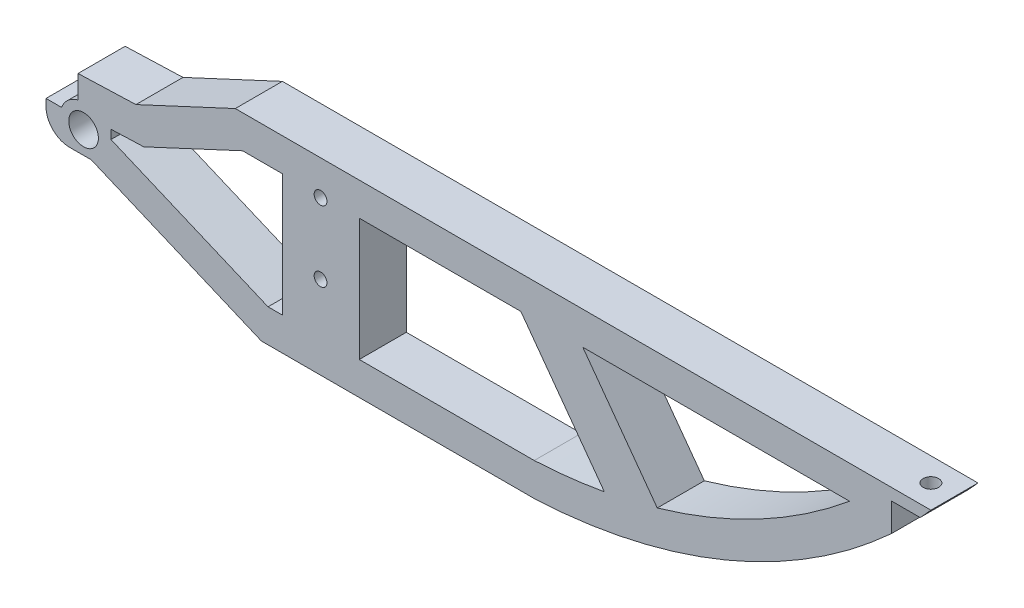
SolidWorks part; units mm, degrees
ref_plane "Front Plane" through (0, 0, 0) normal (0, 0, 1) x (1, 0, 0)
ref_plane "Top Plane" through (0, 0, 0) normal (0, 1, 0) x (1, 0, 0)
ref_plane "Right Plane" through (0, 0, 0) normal (1, 0, 0) x (0, 0, -1)
sketch "Sketch1" plane through (0, 0, 0) normal (0, 0, 1) x (1, 0, 0)
  line L1 (120.65, 25.4) -> (-120.65, 25.4)
  line L2 (120.65, 25.4) -> (120.65, -25.4)
  line L3 (120.65, -25.4) -> (-120.65, -25.4)
  line L4 (-120.65, 25.4) -> (-120.65, -25.4)
  line L5 (120.65, 25.4) -> (-120.65, -25.4) construction
  line L6 (120.65, -25.4) -> (-120.65, 25.4) construction
  point P0 (0, 0)
  dimension "D1" = 241.3
  dimension "D2" = 50.8
extrude "Boss-Extrude1" add sketch "Sketch1" along normal blind 12.7
sketch "Sketch3" plane through (0, 0, 12.7) normal (0, 0, 1) x (1, 0, 0)
  line L0 (0, 0) -> (-120.65, 0) construction
  line L1 (-120.65, 25.4) -> (-120.65, -25.4) construction
  circle A0 centre (-107.95, 0) radius 4
  dimension "D2" = 8
  dimension "D1" = 12.7
extrude "Cut-Extrude1" cut sketch "Sketch3" against normal through all
sketch "Sketch5" plane through (0, 0, 12.7) normal (0, 0, 1) x (1, 0, 0)
  line L0 (-120.65, -25.4) -> (120.65, -25.4) construction
  line L1 (-105.8942, -6.008) -> (-59.9903, -25.4)
  line L2 (-107.95, 6.35) -> (-67.0151, 25.4)
  line L3 (120.65, 25.4) -> (-120.65, 25.4) construction
  line L4 (-67.0151, 25.4) -> (-120.65, 25.4)
  line L5 (-120.65, 25.4) -> (-120.65, -25.4)
  line L6 (-120.65, -25.4) -> (-59.9903, -25.4)
  line L7 (120.65, 25.4) -> (120.65, -25.4)
  line L8 (120.65, -25.4) -> (0, -25.4)
  line L9 (-109.9582, -6.0241) -> (-105.8942, -6.008)
  line L10 (-118.0862, -6.0241) -> (-109.9582, -6.0241)
  line L11 (-118.0862, -6.0241) -> (-118.0862, 2.2309)
  line L12 (-118.0862, 2.2309) -> (-113.8952, 2.2309)
  arc A0 (0, -25.4) -> (120.65, 25.4) centre (6.9175, 126.8429) ccw
  arc A1 (-109.9582, -6.0241) -> (-105.8942, -6.008) centre (-107.95, 0) ccw construction
  arc A2 (-107.95, 6.35) -> (-113.8952, 2.2309) centre (-107.95, 0) ccw
  point P15 (-116.1445, -2.9908)
  line M3 (-120.65, 25.4) -> (-120.65, -25.4)
  line M4 (-120.65, -25.4) -> (120.65, -25.4)
  line M5 (120.65, -25.4) -> (120.65, 25.4)
  line M6 (120.65, 25.4) -> (-120.65, 25.4)
  dimension "D1" = 152.4
  dimension "D2" = 12.7
  dimension "D3" = 45.1505
  dimension "D4" = 45.9039
  dimension "D5" = 8.255
  dimension "D6" = 4.191
  dimension "D7" = 8.128
extrude "Cut-Extrude2" cut sketch "Sketch5" against normal through all contours A2 L2 L1 M6 M3 M4 | A0 L8 M5 region at (-83.2502, -16.4329, 12.7) region at (93.5193, -10.6939, 12.7)
sketch "Sketch6" plane through (0, 0, 12.7) normal (0, 0, 1) x (1, 0, 0)
  line L0 (-107.95, 0) -> (91.396, 0) construction
  arc A0 (13.8349, -25.4) -> (120.65, 25.4) centre (6.9175, 126.8429) ccw construction
  circle A1 centre (19.05, 0) radius 3.1347
  dimension "D1" = 127
sketch "Sketch7" plane through (0, 0, 0) normal (0, 0, -1) x (-1, 0, 0)
  line L0 (44.0204, -2.9977) -> (44.0204, 16.0523) construction
  point P3 (44.0204, -2.9977)
  point P4 (44.0204, 16.0523)
  dimension "D1" = 19.05
sketch "Sketch8" plane through (0, 0, 0) normal (0, 0, -1) x (-1, 0, 0)
  point P0 (44.0204, 16.0523)
  point P3 (44.0204, -2.9977)
hole_wizard "Tap Drill for #8-32 Tap1" positions "Sketch8" profile "Sketch9" hole size "#8-32" standard "ANSI Inch" end condition through all
sketch "Sketch9" plane through (-44.0204, 16.0523, 0) normal (1, 0, 0) x (0, 1, 0)
  line L0 (0, 0) -> (0, 12.7)
  line L1 (0, 12.7) -> (1.7272, 12.7)
  line L2 (1.7272, 12.7) -> (1.7272, 0)
  line L5 (1.7272, 0) -> (0, 0)
  line L11 (0, -6.35) -> (0, 107.95) construction
  dimension "Thru Hole Dia." = 3.4544
  dimension "Thru Hole Depth" = 12.7
ref_plane "Plane1" through (-114.3, 0, 0) normal (-1, 0, 0) x (0, 0, 1)
sketch "Sketch10" plane through (-114.3, 0, 0) normal (-1, 0, 0) x (0, 0, 1)
  line L0 (0, 0) -> (12.7, 0) construction
  line L1 (12.7, -3.1347) -> (12.7, 3.1347) construction
  circle A0 centre (6.0894, 0) radius 1.905
  dimension "D1" = 3.81
extrude "Cut-Extrude3" cut sketch "Sketch10" against normal blind 5.08
sketch "Sketch11" plane through (0, 0, 12.7) normal (0, 0, 1) x (1, 0, 0)
  line L0 (-93.8249, 12.9234) -> (-109.4459, 12.9234) construction
  line L1 (-107.95, 6.35) -> (-67.0151, 25.4) construction
  line L2 (-109.4459, 12.9234) -> (-109.4459, 5.6538) construction
  line L3 (-93.8249, 12.9234) -> (-109.4459, 5.6538)
  line L4 (-93.8249, 12.9234) -> (-109.4459, 12.3779)
  line L5 (-109.4459, 12.3779) -> (-109.4459, 5.6538)
  circle A1 centre (-107.95, 0) radius 4 construction
  dimension "D1" = 15.621
  dimension "D2" = 5.6538
  dimension "D3" = 178
extrude "Boss-Extrude2" add sketch "Sketch11" against normal up to surface (12.7 mm away) up to face at (-45.7476, 16.0523, 0)
sketch "Sketch12" plane through (0, 0, 12.7) normal (0, 0, 1) x (1, 0, 0)
  line L1 (10.0217, 16.51) -> (-33.5733, 16.51)
  line L24 (-33.5733, 16.51) -> (-33.5733, -16.51)
  line L25 (-54.2244, 16.51) -> (-54.2244, -16.51)
  line L26 (-54.2244, 16.51) -> (-65.0478, 16.51)
  line L27 (-33.5733, -16.51) -> (13.63, -16.51)
  line L28 (10.0217, 16.51) -> (32.5572, -14.3581)
  line L29 (26.7339, 16.51) -> (46.8231, -11.0072)
  line L30 (-100.5559, 3.793) -> (-100.5559, 1.3876)
  line L31 (-100.5559, 1.3876) -> (-58.1896, -16.51)
  line L32 (-58.1896, -16.51) -> (13.63, -16.51)
  line L33 (98.6876, 16.51) -> (-65.0478, 16.51)
  line L34 (-65.0478, 16.51) -> (-91.7106, 4.1018)
  line L35 (-91.7106, 4.1018) -> (-100.5559, 3.793)
  line L36 (-100.5559, 3.793) -> (-100.5559, 1.3876)
  line L37 (-100.5559, 1.3876) -> (-58.1896, -16.51)
  line L38 (-58.1896, -16.51) -> (-54.2244, -16.51)
  line L39 (98.6876, 16.51) -> (26.7339, 16.51)
  line L40 (-65.0478, 16.51) -> (-91.7106, 4.1018)
  line L41 (-91.7106, 4.1018) -> (-100.5559, 3.793)
  arc A0 (46.8231, -11.0072) -> (98.6876, 16.51) centre (6.9175, 126.8429) ccw
  arc A10 (13.63, -16.51) -> (98.6876, 16.51) centre (6.9175, 126.8429) ccw
  arc A11 (13.63, -16.51) -> (32.5572, -14.3581) centre (6.9175, 126.8429) ccw
  dimension "D1" = 8.89
extrude "Cut-Extrude4" cut sketch "Sketch12" against normal through all
sketch "Sketch13" plane through (0, 0, 12.7) normal (0, 0, 1) x (1, 0, 0)
  line L0 (-79.3724, -17.2121) -> (-87.4623, -19.4143)
  line L1 (-105.8942, -6.008) -> (-59.9903, -25.4) construction
  line L2 (-87.4623, -19.4143) -> (-89.1909, -13.0643)
  line L4 (-79.3724, -17.2121) -> (-89.1909, -13.0643)
  circle A0 centre (-107.95, 0) radius 4 construction
  dimension "D1" = 90
  dimension "D2" = 6.35
  dimension "D3" = 22.86
fillet "Fillet1" radius 6.35 1 edges at (-118.0862, -6.0241, 6.35)
sketch "Sketch14" plane through (0.0221, -5.5891, 0) normal (0.004, -1, 0) x (1, 0.004, 0)
  line L0 (-109.9812, 0) -> (-109.9812, 12.7) construction
  line L2 (-109.9812, 6.35) -> (-105.9171, 6.35) construction
  line L3 (-105.9171, 0) -> (-105.9171, 12.7) construction
  line L4 (-107.9492, 0) -> (-107.9492, 12.7) construction
  line L5 (-109.9812, 0) -> (-105.9171, 0) construction
  line L6 (-109.9812, 12.7) -> (-105.9171, 12.7) construction
  circle A0 centre (-107.9492, 6.35) radius 1.27
  dimension "D1" = 2.54
extrude "Cut-Extrude5" cut sketch "Sketch14" against normal blind 6.35
sketch "Sketch15" plane through (0, 0, 12.7) normal (0, 0, 1) x (1, 0, 0)
  line L0 (117.6404, 22.225) -> (110.0327, 22.225)
  line L1 (120.65, 22.225) -> (57.15, 22.225) construction
  line L2 (110.0327, 22.225) -> (110.0327, 12.8153)
  line L3 (110.0327, 12.8153) -> (117.6404, 12.8153)
  line L4 (117.6404, 12.8153) -> (117.6404, 22.225)
extrude "Cut-Extrude6" cut sketch "Sketch15" against normal through all
sketch "Sketch16" plane through (0, 0, 12.7) normal (0, 0, 1) x (1, 0, 0)
  line L0 (117.7449, 22.225) -> (117.6404, 22.225)
  line L1 (120.65, 22.225) -> (57.15, 22.225) construction
  line L2 (117.6404, 22.225) -> (117.6404, 22.0792)
  line L3 (117.6404, 22.0792) -> (117.7449, 22.0792)
  line L4 (117.7449, 22.0792) -> (117.7449, 22.225)
  dimension "D1" = 0.1046
  dimension "D2" = 0.1458
extrude "Cut-Extrude8" cut sketch "Sketch16" against normal through all contours L4 L0 L2 L3
sketch "Sketch18" plane through (0, 25.4, 0) normal (0, 1, 0) x (1, 0, 0)
  circle A0 centre (114.3, -6.35) radius 2.0828
extrude "Cut-Extrude9" cut sketch "Sketch18" against normal through all contours A0
